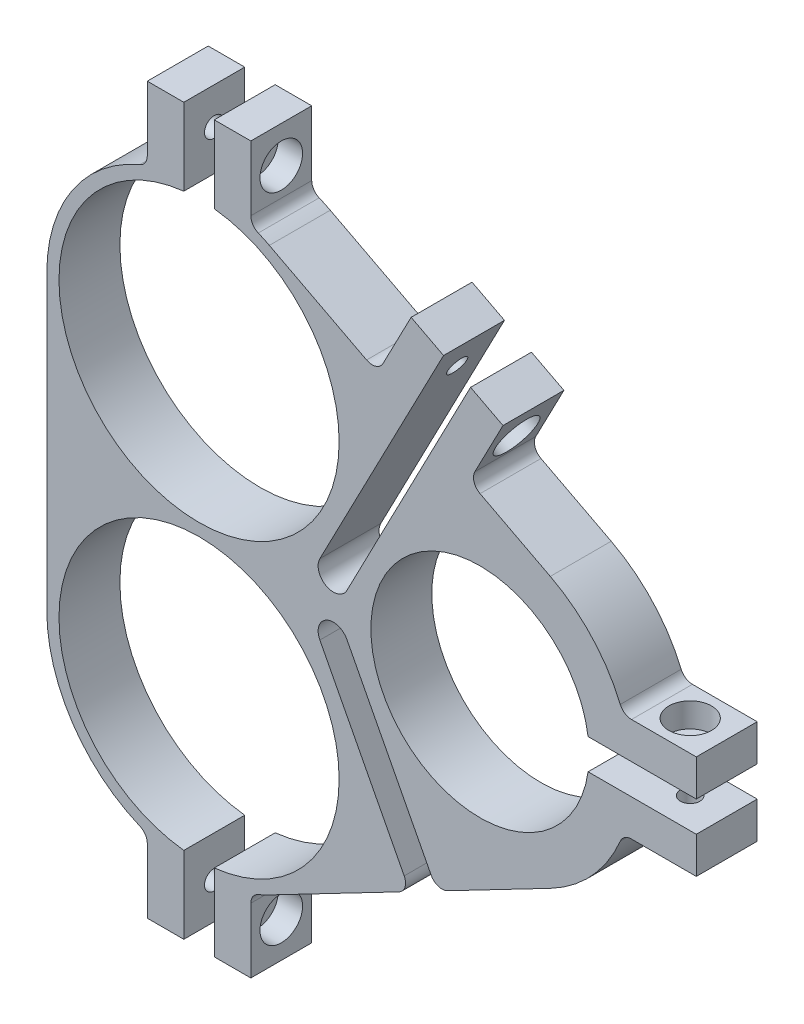
SolidWorks part; units mm, degrees
ref_plane "Front Plane" through (0, 0, 0) normal (0, 0, 1) x (1, 0, 0)
ref_plane "Top Plane" through (0, 0, 0) normal (0, 1, 0) x (1, 0, 0)
ref_plane "Right Plane" through (0, 0, 0) normal (1, 0, 0) x (0, 0, -1)
sketch "Sketch1" plane through (0, 0, 0) normal (0, 0, 1) x (1, 0, 0)
  line L0 (-39.6875, 76.2) -> (-39.6875, 0)
  line L1 (-39.6875, 38.1) -> (73.2318, 38.1) construction
  line L2 (18.3173, 111.4076) -> (46.4834, 96.7537)
  line L3 (3.9688, -36.2962) -> (3.9688, -56.3731)
  line L4 (0, 76.2) -> (0, 0) construction
  line L5 (-13.4938, -37.3231) -> (-13.4938, -56.3731)
  line L6 (3.9688, -56.3731) -> (13.4938, -56.3731)
  line L7 (-3.9688, -56.3731) -> (-13.4938, -56.3731)
  line L8 (13.4938, -37.3231) -> (13.4938, -56.3731)
  line L9 (-3.9687, -36.2962) -> (-3.9688, -56.3731)
  line L10 (18.3173, -35.2076) -> (54.9332, -16.1576)
  line L11 (13.4938, 113.5231) -> (13.4938, 132.5731)
  line L12 (-3.9688, 132.5731) -> (-13.4938, 132.5731)
  line L13 (3.9688, 132.5731) -> (13.4938, 132.5731)
  line L14 (3.9688, 132.5731) -> (3.9688, 112.4962)
  line L15 (-13.4938, 113.5231) -> (-13.4938, 132.5731)
  line L16 (54.9332, 92.3576) -> (61.9747, 88.6941) construction
  line L17 (54.9332, 92.3576) -> (31.487, 47.2919)
  line L18 (-3.9688, 132.5731) -> (-3.9688, 112.4962)
  line L19 (61.9747, 88.6941) -> (38.5286, 43.6284)
  line L20 (31.487, 47.2919) -> (38.5286, 43.6284) construction
  line L21 (54.9332, -16.1576) -> (31.487, 28.9081)
  line L22 (54.9332, 92.3576) -> (63.7255, 109.2572)
  line L23 (3.9688, 132.5731) -> (-3.9688, 132.5731) construction
  line L24 (46.4834, 96.7537) -> (55.2757, 113.6534)
  line L25 (3.9688, -56.3731) -> (-3.9688, -56.3731) construction
  line L26 (63.7255, 109.2572) -> (55.2757, 113.6534)
  line L27 (35.0078, 45.4601) -> (58.454, 90.5259) construction
  line L28 (61.9747, 88.6941) -> (70.767, 105.5938)
  line L29 (70.767, 105.5938) -> (79.2168, 101.1976)
  line L30 (70.4245, 84.298) -> (79.2168, 101.1976)
  line L31 (70.4245, 84.298) -> (91.5491, 73.3076)
  line L32 (61.9747, -12.4941) -> (38.5286, 32.5716)
  line L39 (35.0078, 30.7399) -> (58.454, -14.3259) construction
  line L40 (54.9332, -16.1576) -> (61.9747, -12.4941) construction
  line L41 (61.9747, -12.4941) -> (91.5491, 2.8924)
  line L42 (101.4016, 42.0688) -> (129.6049, 42.0688)
  line L43 (129.6049, 42.0688) -> (129.6049, 51.5938)
  line L44 (129.6049, 51.5938) -> (110.5549, 51.5938)
  line L45 (101.4016, 34.1313) -> (129.6049, 34.1313)
  line L46 (129.6049, 34.1313) -> (129.6049, 24.6063)
  line L47 (129.6049, 24.6063) -> (110.5549, 24.6062)
  arc A0 (3.9688, -36.2962) -> (-3.9687, -36.2962) centre (0, 0) ccw
  arc A1 (-3.9688, 112.4962) -> (3.9688, 112.4962) centre (0, 76.2) ccw
  arc A2 (13.4938, 113.5231) -> (18.3173, 111.4076) centre (0, 76.2) cw
  arc A3 (-39.6875, 0) -> (-13.4938, -37.3231) centre (0, 0) ccw
  arc A4 (101.4016, 42.0688) -> (101.4016, 34.1313) centre (73.2318, 38.1) ccw
  arc A5 (13.4938, -37.3231) -> (18.3173, -35.2076) centre (0, 0) ccw
  arc A6 (-39.6875, 76.2) -> (-13.4938, 113.5231) centre (0, 76.2) cw
  arc A7 (110.5549, 51.5938) -> (110.5549, 24.6062) centre (73.2318, 38.1) ccw construction
  circle A8 centre (0, 0) radius 36.5125 construction
  circle A9 centre (0, 76.2) radius 36.5125 construction
  circle A10 centre (0, 0) radius 39.6875 construction
  circle A11 centre (73.2318, 38.1) radius 36.5125 construction
  circle A12 centre (0, 76.2) radius 39.6875 construction
  arc A13 (91.5491, 73.3076) -> (110.5549, 51.5938) centre (73.2318, 38.1) cw
  circle A14 centre (35.0078, 45.4601) radius 3.9687 construction
  arc A15 (31.487, 47.2919) -> (38.5286, 43.6284) centre (35.0078, 45.4601) ccw
  circle A16 centre (35.0078, 30.7399) radius 3.9687 construction
  arc A17 (31.487, 28.9081) -> (38.5286, 32.5716) centre (35.0078, 30.7399) cw
  arc A18 (110.5549, 24.6062) -> (91.5491, 2.8924) centre (73.2318, 38.1) cw
  point P9 (54.3978, -16.1576)
  point P10 (62.4495, -12.4941)
  point P14 (0, 36.5125)
  point P72 (0, 0)
  point P73 (101.4016, 42.0688)
  dimension "D2" = 56.896
  dimension "D4" = 73.025
  dimension "D5" = 73.025
  dimension "D7" = 79.375
  dimension "D9" = 79.375
  dimension "D10" = 73.025
  dimension "D11" = 7.9375
  dimension "D1" = 7.9375
  dimension "D3" = 76.2
  dimension "D6" = 9.525
  dimension "D8" = 19.05
  dimension "D12" = 82.55
  dimension "D13" = 41.275
  dimension "D14" = 50.8
  dimension "D15" = 19.05
  dimension "D16" = 9.525
  dimension "D17" = 9.525
  dimension "D18" = 7.9375
  dimension "D19" = 19.05
extrude "Extrude1" add sketch "Sketch1" along normal mid plane 15.875
hole_wizard "CBORE for 1/4 Socket Head Cap Screw1" positions "Sketch3" profile "Sketch2" counterbore size "1/4" standard "Ansi Inch" end condition up to next
sketch "Sketch3" plane through (13.4938, 0, 0) normal (1, 0, 0) x (0, 0, -1)
  line L0 (7.9375, 132.5731) -> (-7.9375, 113.5231) construction
  point P0 (0, 123.0481)
sketch "Sketch2" plane through (13.4938, 123.0481, 0) normal (0, 1, 0) x (0, 0, -1)
  line L0 (0, 0) -> (0, 9.525)
  line L1 (0, 9.525) -> (3.3782, 9.525)
  line L3 (3.3782, 9.525) -> (3.3782, 6.35)
  line L4 (3.3782, 6.35) -> (5.5562, 6.35)
  line L5 (5.5562, 6.35) -> (5.5562, 0)
  line L7 (5.5562, 0) -> (0, 0)
  line L11 (0, -6.35) -> (0, 107.95) construction
  dimension "Thru Hole Dia." = 6.7564
  dimension "Thru Hole Depth" = 9.525
  dimension "C'Bore Dia." = 11.1125
  dimension "C'Bore Depth" = 6.35
hole_wizard "1/4-20 Tapped Hole1" positions "Sketch5" profile "Sketch4" tap size "1/4-20" standard "Ansi Inch" end condition through all
sketch "Sketch5" plane through (-3.9687, 0, 0) normal (1, 0, 0) x (0, 0, -1)
  point P0 (0, 123.0481)
sketch "Sketch4" plane through (-3.9688, 123.0481, 0) normal (0, 1, 0) x (0, 0, -1)
  line L0 (0, 0) -> (0, 35.7188)
  line L1 (0, 35.7188) -> (2.5527, 35.7188)
  line L2 (2.5527, 35.7188) -> (2.5527, 0)
  line L5 (2.5527, 0) -> (0, 0)
  line L11 (0, -6.35) -> (0, 107.95) construction
  dimension "Thru Tap Drill Dia." = 5.1054
  dimension "Thru Tap Drill Depth" = 35.7188
cosmetic thread "Hole Thread1" parameters "D2"=6.35
hole_wizard "CBORE for 1/4 Socket Head Cap Screw3" positions "Sketch16" profile "Sketch17" counterbore size "1/4" standard "Ansi Inch" end condition up to next
sketch "Sketch16" plane through (13.4938, 0, 0) normal (1, 0, 0) x (0, 0, -1)
  line L0 (7.9375, -37.3231) -> (-7.9375, -56.3731) construction
  point P0 (0, -46.8481)
sketch "Sketch17" plane through (13.4938, -46.8481, 0) normal (0, 1, 0) x (0, 0, -1)
  line L0 (0, 0) -> (0, 9.525)
  line L1 (0, 9.525) -> (3.3782, 9.525)
  line L3 (3.3782, 9.525) -> (3.3782, 6.35)
  line L4 (3.3782, 6.35) -> (5.5562, 6.35)
  line L5 (5.5562, 6.35) -> (5.5562, 0)
  line L7 (5.5562, 0) -> (0, 0)
  line L11 (0, -6.35) -> (0, 107.95) construction
  dimension "Thru Hole Dia." = 6.7564
  dimension "Thru Hole Depth" = 9.525
  dimension "C'Bore Dia." = 11.1125
  dimension "C'Bore Depth" = 6.35
hole_wizard "1/4-20 Tapped Hole4" positions "Sketch19" profile "Sketch21" tap size "1/4-20" standard "Ansi Inch" end condition through all
sketch "Sketch19" plane through (-3.9687, 0, 0) normal (1, 0, 0) x (0, 0, -1)
  point P0 (0, -46.8481)
sketch "Sketch21" plane through (-3.9687, -46.8481, 0) normal (0, 1, 0) x (0, 0, -1)
  line L0 (0, 0) -> (0, 35.7188)
  line L1 (0, 35.7188) -> (2.5527, 35.7188)
  line L2 (2.5527, 35.7188) -> (2.5527, 0)
  line L5 (2.5527, 0) -> (0, 0)
  line L11 (0, -6.35) -> (0, 107.95) construction
  dimension "Thru Tap Drill Dia." = 5.1054
  dimension "Thru Tap Drill Depth" = 35.7188
cosmetic thread "Hole Thread4" parameters "D2"=6.35
sketch "Sketch29" plane through (20.9079, -10.8777, 0) normal (0.8871, -0.4615, 0) x (0, 0, -1)
  line L0 (7.9375, 126.3361) -> (-7.9375, 107.2861) construction
hole_wizard "CBORE for 1/4 Socket Head Cap Screw4" positions "Sketch30" profile "Sketch31" counterbore size "1/4" standard "ANSI Inch" end condition up to next
sketch "Sketch30" plane through (20.9079, -10.8777, 0) normal (0.8871, -0.4615, 0) x (0, 0, -1)
  line L0 (7.9375, 126.3361) -> (-7.9375, 107.2861) construction
  point P0 (0, 116.8111)
sketch "Sketch31" plane through (74.8207, 92.7478, 0) normal (0, 0, 1) x (0.4615, 0.8871, 0)
  line L0 (0, 0) -> (0, 9.525)
  line L1 (0, 9.525) -> (3.3782, 9.525)
  line L3 (3.3782, 9.525) -> (3.3782, 6.35)
  line L4 (3.3782, 6.35) -> (5.5562, 6.35)
  line L5 (5.5562, 6.35) -> (5.5562, 0)
  line L7 (5.5562, 0) -> (0, 0)
  line L11 (0, -6.35) -> (0, 107.95) construction
  dimension "Thru Hole Dia." = 6.7564
  dimension "Thru Hole Depth" = 9.525
  dimension "C'Bore Dia." = 11.1125
  dimension "C'Bore Depth" = 6.35
hole_wizard "1/4-20 Tapped Hole5" positions "Sketch32" profile "Sketch33" tap size "1/4-20" standard "ANSI Inch" end condition up to next
sketch "Sketch32" plane through (5.4166, -2.818, 0) normal (0.8871, -0.4615, 0) x (0, 0, -1)
  point P0 (0, 116.8111)
sketch "Sketch33" plane through (59.3293, 100.8074, 0) normal (0, 0, 1) x (0.4615, 0.8871, 0)
  line L0 (0, 0) -> (0, 9.525)
  line L1 (0, 9.525) -> (2.5527, 9.525)
  line L2 (2.5527, 9.525) -> (2.5527, 0)
  line L5 (2.5527, 0) -> (0, 0)
  line L11 (0, -6.35) -> (0, 107.95) construction
  dimension "Thru Tap Drill Dia." = 5.1054
  dimension "Thru Tap Drill Depth" = 9.525
cosmetic thread "Hole Thread5" parameters "D2"=6.35
sketch "Sketch41" plane through (0, 51.5938, 0) normal (0, 1, 0) x (1, 0, 0)
  line L0 (129.6049, 7.9375) -> (110.5549, -7.9375) construction
hole_wizard "CBORE for 1/4 Socket Head Cap Screw6" positions "Sketch42" profile "Sketch43" counterbore size "1/4" standard "ANSI Inch" end condition up to next
sketch "Sketch42" plane through (0, 51.5938, 0) normal (0, 1, 0) x (1, 0, 0)
  line L0 (129.6049, 7.9375) -> (110.5549, -7.9375) construction
  point P0 (120.0799, 0)
sketch "Sketch43" plane through (120.0799, 51.5938, 0) normal (1, 0, 0) x (0, 0, 1)
  line L0 (0, 0) -> (0, 9.525)
  line L1 (0, 9.525) -> (3.3782, 9.525)
  line L3 (3.3782, 9.525) -> (3.3782, 6.35)
  line L4 (3.3782, 6.35) -> (5.5562, 6.35)
  line L5 (5.5562, 6.35) -> (5.5563, 0)
  line L7 (5.5563, 0) -> (0, 0)
  line L11 (0, -6.35) -> (0, 107.95) construction
  dimension "Thru Hole Dia." = 6.7564
  dimension "Thru Hole Depth" = 9.525
  dimension "C'Bore Dia." = 11.1125
  dimension "C'Bore Depth" = 6.35
hole_wizard "1/4-20 Tapped Hole7" positions "Sketch44" profile "Sketch45" tap size "1/4-20" standard "ANSI Inch" end condition up to next
sketch "Sketch44" plane through (0, 34.1313, 0) normal (0, 1, 0) x (1, 0, 0)
  line L0 (129.6049, 7.9375) -> (110.5549, -7.9375) construction
  point P0 (120.0799, 0)
sketch "Sketch45" plane through (120.0799, 34.1313, 0) normal (1, 0, 0) x (0, 0, 1)
  line L0 (0, 0) -> (0, 9.525)
  line L1 (0, 9.525) -> (2.5527, 9.525)
  line L2 (2.5527, 9.525) -> (2.5527, 0)
  line L5 (2.5527, 0) -> (0, 0)
  line L11 (0, -6.35) -> (0, 107.95) construction
  dimension "Thru Tap Drill Dia." = 5.1054
  dimension "Thru Tap Drill Depth" = 9.525
cosmetic thread "Hole Thread7" parameters "D2"=6.35
fillet "Fillet1" radius 3.175 10 edges at (13.4938, 113.5231, 0) (-13.4938, 113.5231, 0) (-13.4938, -37.3231, 0) (13.4938, -37.3231, 0) (46.4834, 96.7537, 0) (70.4245, 84.298, 0) (110.5549, 24.6063, 0) (110.5549, 51.5938, 0) (61.9747, -12.4941, 0) (54.9332, -16.1576, 0)
